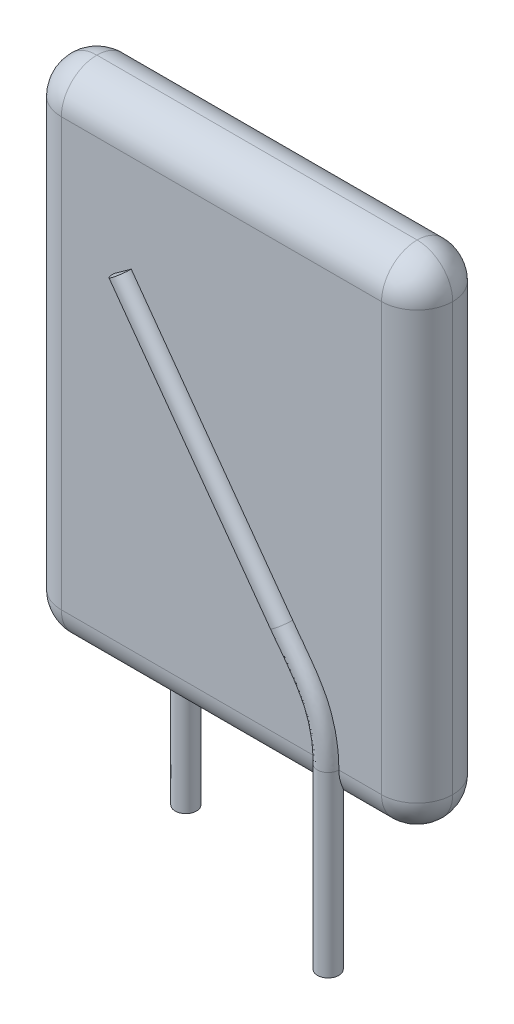
SolidWorks part; units mm, degrees
ref_plane "前视基准面" through (0, 0, 0) normal (0, 0, 1) x (1, 0, 0)
ref_plane "上视基准面" through (0, 0, 0) normal (0, 1, 0) x (1, 0, 0)
ref_plane "右视基准面" through (0, 0, 0) normal (1, 0, 0) x (0, 0, -1)
sketch "草图1" plane through (0, 0, 0) normal (0, 0, 1) x (1, 0, 0)
  line L0 (0, 18.5478) -> (0, -18.5478) construction
  line L1 (-5.5, 14) -> (5.5, 14)
  line L2 (-5.5, 14) -> (-5.5, 0)
  line L3 (-5.5, 0) -> (5.5, 0)
  line L4 (5.5, 14) -> (5.5, 0)
  point P4 (5.7674, 18.5478)
  point P8 (0, 0)
  dimension "D1" = 11
  dimension "D2" = 14
extrude "凸台-拉伸1" add sketch "草图1" along normal mid plane 2
fillet "圆角1" radius 1 8 edges at (0, 0, -1) (5.5, 7, -1) (0, 14, -1) (-5.5, 7, -1) (0, 14, 1) (5.5, 7, 1) (0, 0, 1) (-5.5, 7, 1)
sketch "草图2" plane through (0, 0, 1) normal (0, 0, 1) x (1, 0, 0)
  line L0 (-2.7771, 10.0984) -> (1.7605, 3.8226)
  line L2 (3, 1) -> (3, -4)
  line L3 (-4.5, 1) -> (4.5, 1) construction
  spline S0 degree 3 poles (1.7605, 3.8226) (2.1011, 3.3515) (2.7528, 2.5748) (3, 1.6041) (3, 1) knots 0 0 0 0 0.50314 1 1 1 1
  point P2 (1.7605, 3.8226)
  point P5 (2.8427, 2.1914)
  point P7 (2.6545, 2.5208)
  point P8 (-2.7771, 10.0984)
  dimension "D1" = 3
  dimension "D2" = 5
sweep "扫描1" add path "草图2" circular profile diameter 0.6 parameters "D3"=0.6
mirror "镜向1" [suppressed] about plane through (0, 0, 0) normal (1, 0, 0)
ref_axis "基准轴1" through (0, 14.9, 0) along (0, -1, 0)
pattern_circular "阵列(圆周)1" count 2 over 360 about axis through (0, 14.9, 0) along (0, -1, 0) of bodies 107
